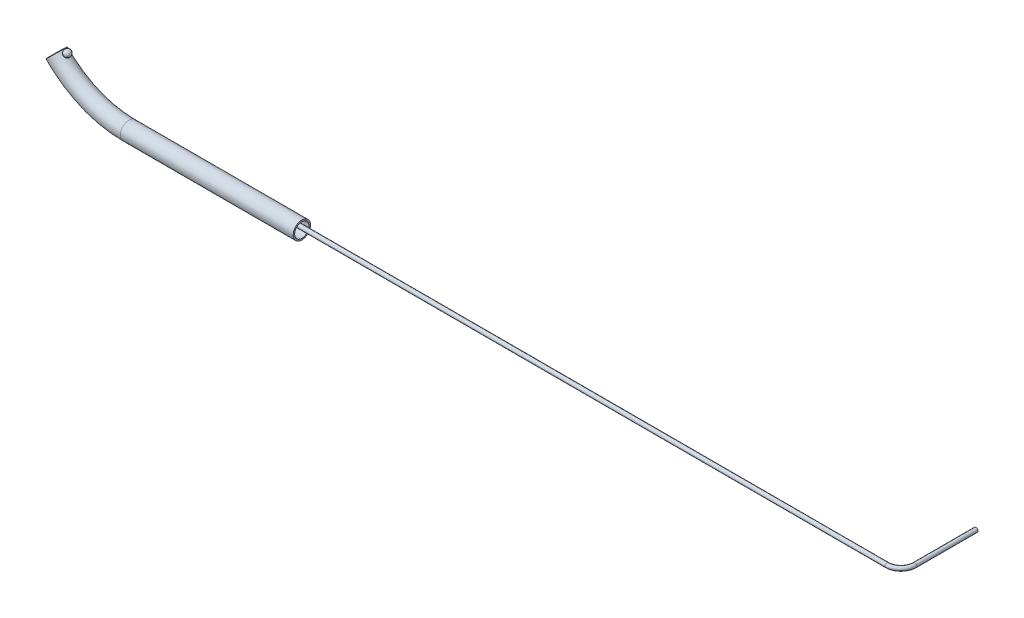
SolidWorks part; units mm, degrees
ref_plane "Front Plane" through (0, 0, 0) normal (0, 0, 1) x (1, 0, 0)
ref_plane "Top Plane" through (0, 0, 0) normal (0, 1, 0) x (1, 0, 0)
ref_plane "Right Plane" through (0, 0, 0) normal (1, 0, 0) x (0, 0, -1)
ref_axis "Axis1" through (-232.0518, 0, 0) along (1, 0, 0)
sketch "Sketch4" plane through (0, 0, 0) normal (0, 0, 1) x (1, 0, 0)
  line L0 (-218.053, 283.5718) -> (61.923, 683.419) construction
  line L1 (-68.365, 0) -> (-65.9542, 0)
  arc A0 (-68.365, 0) -> (-73.5499, 2.2253) centre (-68.365, 7.1532) cw
  point P2 (-73.5499, 2.2253)
  point P3 (-68.365, 0)
sketch "Sketch1" plane through (0, 0, 0) normal (1, 0, 0) x (0, 0, -1)
  circle A0 centre (0, 0) radius 0.61
  circle A1 centre (0, 0) radius 0.39
  dimension "D1" = 1.22
  dimension "D2" = 0.22
extrude "Boss-Extrude1" [suppressed] add sketch "Sketch1" along normal blind 10
ref_plane "Plane1" through (-65.9542, 0, 0) normal (1, 0, 0) x (0, 0, -1)
sketch "Sketch5" plane through (-65.9542, 0, 0) normal (1, 0, 0) x (0, 0, -1)
  circle A0 centre (0, 0) radius 0.6223
  circle A1 centre (0, 0) radius 0.5143
  dimension "D1" = 1.2446
  dimension "D2" = 1.0287
sweep "Sweep2" add profiles "Sketch5" path "Sketch4"
extrude "Boss-Extrude2" add sketch "Sketch5<2>" along normal blind 10
sketch "Sketch5<2>" plane through (-65.9542, 0, 0) normal (1, 0, 0) x (0, 0, -1) same geometry as "Sketch5"
sketch "Sketch6" plane through (0, 0, 0) normal (0, 0, 1) x (1, 0, 0)
  line L0 (-72.7874, 2.8286) -> (-72.7874, 2.3286) construction
  line L1 (-72.9491, 2.3879) -> (-72.6257, 2.7693)
  circle A0 centre (-72.7874, 2.5786) radius 0.25 construction
  arc A1 (-72.9491, 2.3879) -> (-72.6257, 2.7693) centre (-72.7874, 2.5786) ccw
  dimension "D1" = 0.5
revolve "Revolve2" add sketch "Sketch6" angle 360 about L1
sketch "Sketch7" plane through (0, 0, 0) normal (0, 0, 1) x (1, 0, 0)
  line L0 (-68.365, -0.6223) -> (-55.9542, -0.6223) construction
  line L1 (-68.365, -0.6223) -> (-55.9542, -0.6223) construction
  line L2 (-68.365, 0.1777) -> (-55.9542, 0.1777)
  arc A1 (-74.001, 1.7966) -> (-68.365, -0.6223) centre (-68.365, 7.1532) ccw construction
  arc A2 (-74.001, 1.7966) -> (-68.365, -0.6223) centre (-68.365, 7.1532) ccw construction
  arc A3 (-73.4211, 2.3477) -> (-68.365, 0.1777) centre (-68.365, 7.1532) ccw
  dimension "D1" = 0.8
sketch "Sketch8" plane through (-36.0182, 37.8966, 0) normal (-0.6889, 0.7248, 0) x (0.7248, 0.6889, 0)
  circle A0 centre (-51.6014, 0) radius 0.15
  point P0 (-51.6014, 0)
  dimension "D1" = 0.3
sweep "Sweep3" add profiles "Sketch8" path "Sketch7"
sketch "Sketch9" plane through (-55.9542, 0, 0) normal (1, 0, 0) x (0, 0, -1)
  circle A0 centre (0, 0.1777) radius 0.15 construction
  circle A1 centre (0, 0.1777) radius 0.15
extrude "Boss-Extrude3" add sketch "Sketch9" along normal blind 40
sketch "Sketch12" plane through (-15.9542, 0, 0) normal (1, 0, 0) x (0, 0, -1)
  line L0 (0.15, 0.1777) -> (-0.15, 0.1777)
  circle A0 centre (0, 0.1777) radius 0.15 construction
ref_plane "Plane2" through (0, 0.1777, 0) normal (0, 1, 0) x (0, 0, 1)
sketch "Sketch11" plane through (-15.9542, 0, 0) normal (1, 0, 0) x (0, 0, -1)
  circle A0 centre (0, 0.1777) radius 0.15 construction
  circle A1 centre (0, 0.1777) radius 0.15
sketch "Sketch10" plane through (-32.5249, 0.1777, -2.7436) normal (0, -1, 0) x (1, 0, 0)
  line L1 (16.5707, 2.7436) -> (18.5707, 2.7436)
  line L2 (16.5707, 2.007) -> (16.5707, 3.4802) construction
  line L3 (19.5707, 1.7436) -> (19.5707, -2.6379)
  arc A0 (19.5707, 1.7436) -> (18.5707, 2.7436) centre (18.5707, 1.7436) ccw
  point P6 (19.5707, 2.7436)
  dimension "D1" = 3
  dimension "D2" = 1
sweep "Sweep4" add profiles "Sketch11" path "Sketch10"
equation "\"Do\"=8.5mm"
equation "\"Lo\"=10"
equation "\"screw_diam\" = 3.5mm"
equation "\"wheel_Do\"=12.5mm"
equation "\"wheel_thickness\"=4mm"
equation "\"Collet_diameter\"=4.3"
equation "\"clearance\"= 0.5mm"
equation "\"handle_body_width\" = 10mm"
equation "\"finger_diameter\"=35"
equation "\"collet_lid_diameter\"=10"
equation "\"screw_cap_diam\"=5.15"
equation "\"handle_thickness\"=12.5mm"
equation "\"post_hole_diam\"=2"
equation "\"roll_rod_diam\"= 6.5 "
equation "\"roll_rod_length\"=6.6"
equation "\"disc_diam\"=5"
equation "\"disc_width\"=1.5"
equation "\"arm_width\"=5"
equation "\"arm_thickness\"=4.5"
equation "\"wheel_total_diam\"=30"
equation "\"spring_diam\"=4.1"
equation "\"collet_length\" = 18.75mm"
equation "\"tip_length\" = 40mm"
equation "\"cable_tube_OD\"=0.508"
equation "\"cable_OD\" = 0.3mm"
equation "\"D1@Sketch8\"=\"cable_OD\""
